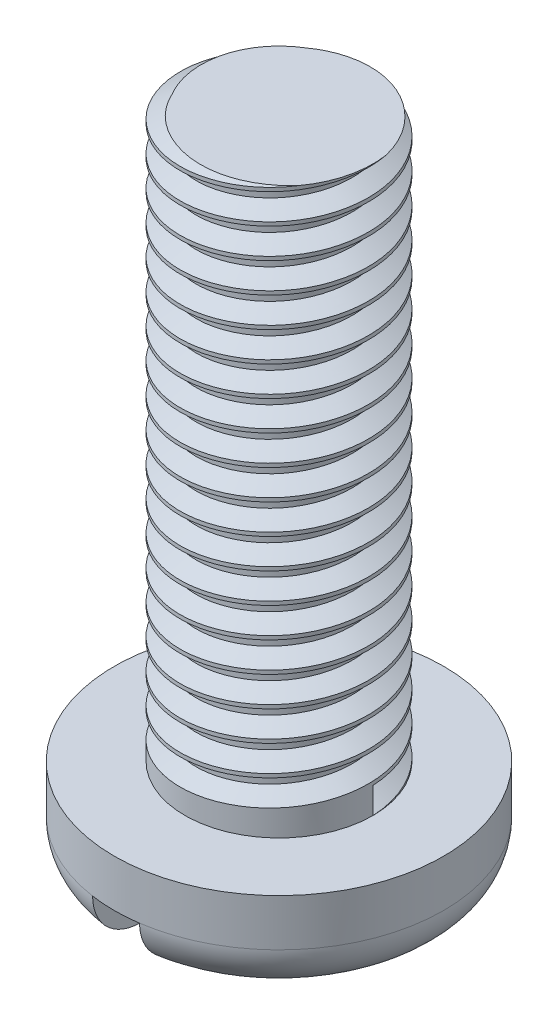
SolidWorks part; units mm, degrees
material "普通碳钢"
ref_plane "前视基准面" through (0, 0, 0) normal (0, 0, 1) x (1, 0, 0)
ref_plane "上视基准面" through (0, 0, 0) normal (0, 1, 0) x (1, 0, 0)
ref_plane "右视基准面" through (0, 0, 0) normal (1, 0, 0) x (0, 0, -1)
sketch "草图1" plane through (0, 0, 0) normal (0, 1, 0) x (1, 0, 0)
  circle A0 centre (0, 0) radius 1.75
  dimension "D1" = 3.5
extrude "凸台-拉伸1" add sketch "草图1" along normal blind 0.5 and the other way blind 0.5
sketch "草图2" plane through (0, 0.5, 0) normal (0, 1, 0) x (1, 0, 0)
  circle A0 centre (0, 0) radius 1
  dimension "D1" = 2
extrude "凸台-拉伸2" add sketch "草图2" along normal blind 6
thread "螺纹线1" pitch 0.3175 method cut profile "螺纹线轮廓1" start angle 0, offset 0, length 10, pitch 0.3175, diameter 2
ref_plane "基准面1" through (1, 0.5, 0) normal (0, 0, 1) x (1, 0, 0)
sketch "螺纹线轮廓1" plane through (1, 0.5, 0) normal (0, 0, 1) x (1, 0, 0)
  line L0 (0, 0) -> (0, 0.3175) construction
  line L11 (0, 0) -> (0, 0.2778)
  line L12 (0, 0.2778) -> (-0.1719, 0.1786)
  line L13 (-0.1719, 0.1786) -> (-0.1719, 0.0992)
  line L15 (-0.1719, 0.0992) -> (0, 0)
  line L17 (-0.1719, 0.1389) -> (0, 0.1389) construction
  point P2 (0, 0)
  dimension "Pitch" = 0.3175
  dimension "Profile_Angle" = 60
  dimension "Profile_Land" = 0.0794
  dimension "Profile_Height" = 0.1719
fillet "圆角3" radius 0.5 1 edges at (0, -0.5, 1.75)
sketch "草图5" plane through (0, -0.5, 0) normal (0, -1, 0) x (1, 0, 0)
  line L6 (0.25, 4.7182) -> (-0.25, 4.7182)
  line L11 (0.25, 4.7182) -> (0.25, -4.7182)
  line L12 (0.25, -4.7182) -> (-0.25, -4.7182)
  line L15 (-0.25, 4.7182) -> (-0.25, -4.7182)
  line L16 (0.25, 4.7182) -> (-0.25, -4.7182) construction
  line L18 (0.25, -4.7182) -> (-0.25, 4.7182) construction
  point P0 (0, 0)
  dimension "D1" = 0.5
extrude "切除-拉伸1" cut sketch "草图5" against normal blind 0.5
